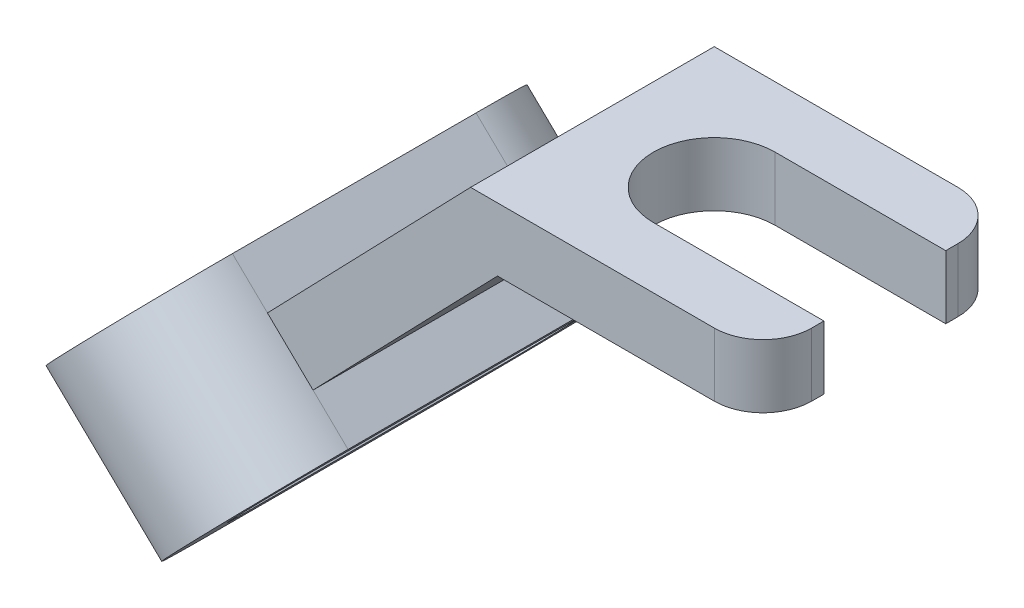
SolidWorks part; units mm, degrees
ref_plane "정면" through (0, 0, 0) normal (0, 0, 1) x (1, 0, 0)
ref_plane "윗면" through (0, 0, 0) normal (0, 1, 0) x (1, 0, 0)
ref_plane "우측면" through (0, 0, 0) normal (1, 0, 0) x (0, 0, -1)
sketch "Sketch1" plane through (0, 0, 0) normal (0, 0, 1) x (1, 0, 0)
  line L0 (54.4818, 0) -> (0, 0)
  line L1 (0, 0) -> (-51.7394, -53.5777)
  line L2 (54.4818, 13) -> (-5.5182, 13)
  line L3 (-5.5182, 13) -> (-61.0908, -44.5472)
  line L4 (54.4818, 0) -> (54.4818, 13)
  line L5 (-51.7394, -53.5777) -> (-61.0908, -44.5472)
  dimension "D2" = 60
  dimension "D3" = 80
  dimension "D4" = 134
  dimension "D1" = 13
extrude "Boss-Extrude1" add sketch "Sketch1" along normal blind 50 contours L3 L5 L1 L0 L4 L2
ref_plane "Plane1" through (-4.6757, 4.5153, 0) normal (0.7193, -0.6947, 0) x (0, 0, -1)
sketch "Sketch4" plane through (-4.6757, 4.5153, 0) normal (0.7193, -0.6947, 0) x (0, 0, -1)
  line L0 (-50, -74.4818) -> (0, -74.4818) construction
  line L1 (-50, -54.4818) -> (0, -54.4818)
  line L2 (-50, -94.4818) -> (0, -94.4818)
  line L3 (-50, -74.4818) -> (0, -74.4818) construction
  line L4 (-50, -65.4818) -> (0, -65.4818)
  line L5 (-50, -83.4818) -> (0, -83.4818)
  arc A0 (-50, -54.4818) -> (-50, -94.4818) centre (-50, -74.4818) ccw
  arc A1 (0, -94.4818) -> (0, -54.4818) centre (0, -74.4818) ccw
  arc A2 (-50, -65.4818) -> (-50, -83.4818) centre (-50, -74.4818) ccw
  arc A3 (0, -83.4818) -> (0, -65.4818) centre (0, -74.4818) ccw
  point P4 (-25, -74.4818)
  point P9 (-25, -74.4818)
  point P16 (0, 0)
  dimension "D1" = 20
  dimension "D2" = 9
extrude "Boss-Extrude2" add sketch "Sketch4" along normal mid plane 33
extrude "Cut-Extrude1" cut sketch "Sketch4<2>" against normal mid plane 33 contours L5 A3 L4 A2 region at (-56.4151, -49.0625, 25)
sketch "Sketch4<2>" plane through (-4.6757, 4.5153, 0) normal (0.7193, -0.6947, 0) x (0, 0, -1) same geometry as "Sketch4"
sketch "Sketch6" plane through (0, 13, 0) normal (0, 1, 0) x (1, 0, 0)
  line L0 (19.4818, -25) -> (54.4818, -25) construction
  line L1 (54.4818, -50) -> (54.4818, 0) construction
  line L2 (19.4818, -12.5) -> (54.4818, -12.5)
  line L3 (19.4818, -37.5) -> (54.4818, -37.5)
  arc A0 (19.4818, -12.5) -> (19.4818, -37.5) centre (19.4818, -25) ccw
  arc A1 (54.4818, -37.5) -> (54.4818, -12.5) centre (54.4818, -25) ccw
  point P4 (36.9818, -25)
  dimension "D2" = 12.5
  dimension "D1" = 35
extrude "Cut-Extrude2" cut sketch "Sketch6" against normal up to next
fillet "Fillet1" radius 10 2 edges at (54.4818, 6.5, 0) (54.4818, 6.5, 50)
